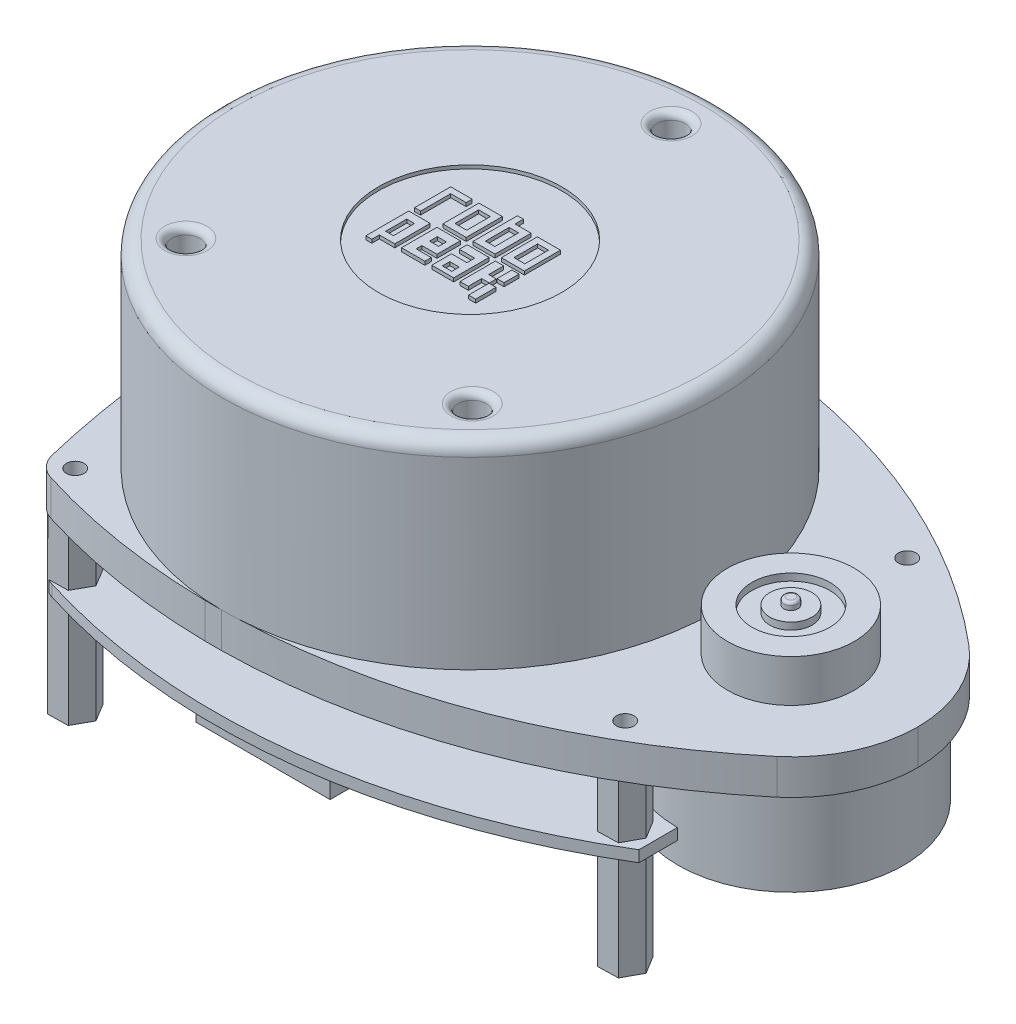
SolidWorks part; units mm, degrees
material "ABS"
ref_plane "Спереди" through (0, 0, 0) normal (0, 0, 1) x (1, 0, 0)
ref_plane "Сверху" through (0, 0, 0) normal (0, 1, 0) x (1, 0, 0)
ref_plane "Справа" through (0, 0, 0) normal (1, 0, 0) x (0, 0, -1)
sketch "Эскиз1" plane through (0, 0, 0) normal (0, 1, 0) x (1, 0, 0)
  line L1 (-49.25, 35) -> (49.25, 35)
  line L2 (-49.25, 35) -> (-49.25, -35)
  line L3 (-49.25, -35) -> (49.25, -35)
  line L4 (49.25, 35) -> (49.25, -35)
  line L5 (-49.25, 35) -> (49.25, -35) construction
  line L6 (-49.25, -35) -> (49.25, 35) construction
  point P0 (0, 0)
  dimension "D1" = 98.5
  dimension "D2" = 70
extrude "Бобышка-Вытянуть1" add sketch "Эскиз1" along normal blind 5
sketch "Эскиз2" plane through (0, 5, 0) normal (0, 1, 0) x (1, 0, 0)
  line L0 (-49.25, 35) -> (-49.25, -35) construction
  circle A0 centre (-14.25, 0) radius 35
  point P2 (-49.25, 0)
  point P3 (-49.25, 0)
extrude "Бобышка-Вытянуть2" add sketch "Эскиз2" along normal blind 28.1
sketch "Эскиз3" plane through (0, 33.1, 0) normal (0, 1, 0) x (1, 0, 0)
  line L0 (-14.25, 0) -> (-14.25, 50000) construction
  line L1 (-14.25, -20) -> (-26.2883, -20) construction
  line L2 (-49.25, -35) -> (-14.25, -35) construction
  circle A0 centre (-14.25, 28.5) radius 2
  circle A1 centre (-34.5539, -20) radius 2
  circle A2 centre (6.0539, -20) radius 2
  arc A3 (-49.25, 0) -> (-14.25, -35) centre (-14.25, 0) ccw construction
  circle A4 centre (-14.25, 0) radius 35 construction
  dimension "D2" = 4
  dimension "D1" = 6.5
  dimension "D3" = 15
  dimension "D4" = 28.5
  dimension "D5" = 28.5
extrude "Вырез-Вытянуть1" cut sketch "Эскиз3" against normal blind 5
fillet "Скругление1" radius 2 1 edges at (-14.25, 33.1, 35)
fillet "Скругление2" radius 1 3 edges at (6.0539, 33.1, 22) (-34.5539, 33.1, 22) (-14.25, 33.1, -26.5)
sketch "Эскиз4" plane through (0, 33.1, 0) normal (0, 1, 0) x (1, 0, 0)
  line L0 (-22.1152, -6.9149) -> (-22.1152, -0.8316)
  line L1 (-22.1152, -0.8316) -> (-19.0735, -0.8316)
  line L2 (-19.0735, -0.8316) -> (-19.0735, -5.8538)
  line L3 (-19.0735, -5.8538) -> (-21.2663, -5.8538)
  line L4 (-21.2663, -5.8538) -> (-21.2663, -6.9149)
  line L5 (-21.2663, -6.9149) -> (-22.1152, -6.9149)
  line L6 (-22.1152, 0) -> (-22.1152, 5.1201)
  line L7 (-22.1152, 5.1201) -> (-19.0735, 5.1201)
  line L8 (-19.0735, 5.1201) -> (-19.0735, 4.2707)
  line L9 (-19.0735, 4.2707) -> (-21.2663, 4.2707)
  line L10 (-21.2663, 4.2707) -> (-21.2663, 0)
  line L11 (-21.2663, 0) -> (-22.1152, 0)
  line L12 (-21.2663, -1.9579) -> (-20.1699, -1.9579)
  line L13 (-20.1699, -1.9579) -> (-20.1699, -4.9509)
  line L14 (-20.1699, -4.9509) -> (-21.2663, -4.9509)
  line L15 (-21.2663, -4.9509) -> (-21.2663, -1.9579)
  line L16 (-13.8296, 0) -> (-13.8296, 6.293)
  line L17 (-18.1168, 0) -> (-14.8003, 0)
  line L18 (-18.1168, 0) -> (-18.1168, 5.1201)
  line L19 (-18.1168, 5.1201) -> (-14.8003, 5.1201)
  line L20 (-14.8003, 0) -> (-14.8003, 5.1201)
  line L21 (-9.8255, 5.1201) -> (-6.5494, 5.1201)
  line L22 (-9.8255, 5.1201) -> (-9.8255, 0)
  line L23 (-9.8255, 0) -> (-6.5494, 0)
  line L24 (-6.5494, 5.1201) -> (-6.5494, 0)
  line L25 (-8.9357, 4.2707) -> (-7.3988, 4.2707)
  line L26 (-8.9357, 4.2707) -> (-8.9357, 0.9137)
  line L27 (-8.9357, 0.9137) -> (-7.3988, 0.9137)
  line L28 (-7.3988, 4.2707) -> (-7.3988, 0.9137)
  line L29 (-17.3079, 4.2707) -> (-15.6497, 4.2707)
  line L30 (-17.3079, 4.2707) -> (-17.3079, 0.9137)
  line L31 (-17.3079, 0.9137) -> (-15.6497, 0.9137)
  line L32 (-15.6497, 4.2707) -> (-15.6497, 0.9137)
  line L33 (-12.9802, 4.2707) -> (-11.6455, 4.2707)
  line L34 (-12.9802, 4.2707) -> (-12.9802, 0.9137)
  line L35 (-12.9802, 0.9137) -> (-11.6455, 0.9137)
  line L36 (-11.6455, 4.2707) -> (-11.6455, 0.9137)
  line L37 (-12.9802, -4.142) -> (-11.6455, -4.142)
  line L38 (-12.9802, -4.142) -> (-12.9802, -5.1936)
  line L39 (-12.9802, -5.1936) -> (-11.6455, -5.1936)
  line L40 (-11.6455, -4.142) -> (-11.6455, -5.1936)
  line L41 (-16.9439, -1.9579) -> (-15.6497, -1.9579)
  line L42 (-16.9439, -1.9579) -> (-16.9439, -3.0499)
  line L43 (-16.9439, -3.0499) -> (-15.6497, -3.0499)
  line L44 (-15.6497, -1.9579) -> (-15.6497, -3.0499)
  line L46 (-7.5508, -0.7643) -> (-6.5494, -0.7643)
  line L47 (-7.5508, -0.7643) -> (-7.5508, -2.8858)
  line L48 (-7.5508, -2.8858) -> (-6.5494, -2.8858)
  line L49 (-6.5494, -0.7643) -> (-6.5494, -2.8858)
  line L50 (-6.5494, -6.9149) -> (-7.5508, -6.9149)
  line L51 (-6.5494, -6.9149) -> (-6.5494, -4.0216)
  line L52 (-6.5494, -4.0216) -> (-7.5508, -4.0216)
  line L53 (-13.8296, 6.293) -> (-12.9802, 6.293)
  line L54 (-12.9802, 6.293) -> (-12.9802, 5.1201)
  line L55 (-12.9802, 5.1201) -> (-10.7153, 5.1201)
  line L56 (-10.7153, 5.1201) -> (-10.7153, 0)
  line L57 (-10.7153, 0) -> (-13.8296, 0)
  line L58 (-9.8255, -0.8316) -> (-8.6437, -0.8316)
  line L59 (-8.6437, -0.8316) -> (-8.6437, -2.9608)
  line L60 (-8.6437, -2.9608) -> (-7.5508, -2.9608)
  line L61 (-9.8255, -0.8316) -> (-9.8255, -5.8538)
  line L62 (-9.8255, -5.8538) -> (-8.6437, -5.8538)
  line L63 (-8.6437, -5.8538) -> (-8.6437, -3.9573)
  line L64 (-8.6437, -3.9573) -> (-7.5508, -3.9573)
  line L65 (-7.5508, -2.9608) -> (-7.5508, -3.9573)
  line L66 (-13.8296, -0.8316) -> (-10.7153, -0.8316)
  line L67 (-10.7153, -0.8316) -> (-10.7153, -5.8538)
  line L68 (-10.7153, -5.8538) -> (-13.8296, -5.8538)
  line L69 (-13.8296, -5.8538) -> (-13.8296, -3.0499)
  line L70 (-13.8296, -3.0499) -> (-11.6455, -3.0499)
  line L71 (-11.6455, -3.0499) -> (-11.6455, -1.9408)
  line L72 (-11.6455, -1.9408) -> (-13.8296, -1.9408)
  line L73 (-13.8296, -1.9408) -> (-13.8296, -0.8316)
  line L74 (-18.1168, -0.8316) -> (-14.8003, -0.8316)
  line L75 (-14.8003, -0.8316) -> (-14.8003, -4.142)
  line L76 (-14.8003, -4.142) -> (-16.9439, -4.142)
  line L77 (-16.9439, -4.142) -> (-16.9439, -4.9509)
  line L78 (-16.9439, -4.9509) -> (-14.8003, -4.9509)
  line L79 (-14.8003, -4.9509) -> (-14.8003, -5.8538)
  line L80 (-14.8003, -5.8538) -> (-18.1168, -5.8538)
  line L81 (-18.1168, -5.8538) -> (-18.1168, -0.8316)
  line L82 (-7.5508, -6.9149) -> (-7.5508, -4.0216)
  circle A0 centre (-14.25, 0) radius 13
  dimension "D1" = 26
extrude "Вырез-Вытянуть3" cut sketch "Эскиз4" against normal blind 0.5 contours A0 L50 L82 L52 L51 L72 L73 L66 L67 L68 L69 L70 L71 L56 L57 L16 L53 L54 L55 L10 L11 L6 L7 L8 L9 L4 L5 L0 L1 L2 L3 L20 L17 L18 L19 L21 L24 L23 L22 L46 L49 L48 L47 | L32 L29 L30 L31 | L36 L33 L34 L35 | L28 L25 L26 L27 | L44 L41 L42 L43 | L15 L14 L13 L12 | L37 L40 L39 L38 region at (-20.7181, 33.1, 3.4544) region at (-8.1672, 33.1, -2.5922) region at (-16.4788, 33.1, -2.5922) region at (-12.3129, 33.1, -2.5922) region at (-16.2968, 33.1, 2.5039) region at (-14.2871, 33.1, -0.0991)
sketch "Эскиз5" plane through (0, 5, 0) normal (0, 1, 0) x (1, 0, 0)
  line L0 (-42.25, 30.7255) -> (-42.25, -39.5827) construction
  line L1 (27.75, 26.9972) -> (27.75, -49973.0028) construction
  line L2 (-49.25, 0) -> (49950.75, 0) construction
  circle A0 centre (-14.25, 0) radius 33 construction
  circle A1 centre (-42.25, 28) radius 1.25
  circle A2 centre (27.75, 20) radius 1.25
  circle A3 centre (27.75, -20) radius 1.25
  circle A4 centre (-42.25, -28) radius 1.25
  point P4 (-14.25, 33)
  dimension "D1" = 28
  dimension "D3" = 2.5
  dimension "D2" = 42
  dimension "D4" = 28
  dimension "D5" = 20
extrude "Вырез-Вытянуть4" cut sketch "Эскиз5" against normal blind 5
sketch "Эскиз6" plane through (0, 5, 0) normal (0, 1, 0) x (1, 0, 0)
  line L0 (49.25, 0) -> (50049.25, 0) construction
  line L1 (49.25, -35) -> (49.25, 35) construction
  circle A0 centre (31.25, 0) radius 9
  arc A1 (-14.25, -35) -> (-14.25, 35) centre (-14.25, 0) ccw construction
  point P4 (49.25, 0)
  dimension "D1" = 18
  dimension "D2" = 45.5
extrude "Бобышка-Вытянуть3" add sketch "Эскиз6" along normal blind 7
sketch "Эскиз7" plane through (0, 12, 0) normal (0, 1, 0) x (1, 0, 0)
  circle A0 centre (31.25, 0) radius 9
  circle A1 centre (31.25, 0) radius 0.9935
extrude "Вырез-Вытянуть5" cut sketch "Эскиз7" against normal blind 1
sketch "Эскиз8" plane through (0, 11, 0) normal (0, 1, 0) x (1, 0, 0)
  circle A0 centre (31.25, 0) radius 3.0011
  circle A1 centre (31.25, 0) radius 5.5217
extrude "Вырез-Вытянуть6" cut sketch "Эскиз8" against normal blind 1
fillet "Скругление3" radius 0.4 1 edges at (31.25, 12, 0.9935)
sketch "Эскиз9" plane through (0, 5, 0) normal (0, 1, 0) x (1, 0, 0)
  circle A0 centre (31.25, 0) radius 16
  dimension "D1" = 32
extrude "Бобышка-Вытянуть4" add sketch "Эскиз9" against normal blind 18
sketch "Эскиз10" plane through (0, 0, 0) normal (0, -1, 0) x (1, 0, 0)
  line L0 (-49.25, 0) -> (49950.75, 0) construction
  line L1 (-40.8546, 25.4729) -> (-39.3638, 27.9449)
  line L2 (-39.3638, 27.9449) -> (-40.7592, 30.472)
  line L3 (-40.7592, 30.472) -> (-43.6454, 30.5271)
  line L4 (-43.6454, 30.5271) -> (-45.1362, 28.0551)
  line L5 (-45.1362, 28.0551) -> (-43.7408, 25.528)
  line L6 (-43.7408, 25.528) -> (-40.8546, 25.4729)
  line L7 (29.2571, 22.4621) -> (26.3713, 22.5363)
  line L8 (26.3713, 22.5363) -> (24.8642, 20.0742)
  line L9 (24.8642, 20.0742) -> (26.2429, 17.5379)
  line L10 (26.2429, 17.5379) -> (29.1287, 17.4637)
  line L11 (29.1287, 17.4637) -> (30.6358, 19.9258)
  line L12 (30.6358, 19.9258) -> (29.2571, 22.4621)
  line L13 (30.6358, -19.9258) -> (29.2571, -22.4621)
  line L14 (29.1287, -17.4637) -> (30.6358, -19.9258)
  line L15 (26.2429, -17.5379) -> (29.1287, -17.4637)
  line L16 (24.8642, -20.0742) -> (26.2429, -17.5379)
  line L17 (26.3713, -22.5363) -> (24.8642, -20.0742)
  line L18 (29.2571, -22.4621) -> (26.3713, -22.5363)
  line L19 (-43.7408, -25.528) -> (-40.8546, -25.4729)
  line L20 (-45.1362, -28.0551) -> (-43.7408, -25.528)
  line L21 (-43.6454, -30.5271) -> (-45.1362, -28.0551)
  line L22 (-40.7592, -30.472) -> (-43.6454, -30.5271)
  line L23 (-39.3638, -27.9449) -> (-40.7592, -30.472)
  line L24 (-40.8546, -25.4729) -> (-39.3638, -27.9449)
  circle A0 centre (-42.25, 28) radius 2.5 construction
  circle A1 centre (27.75, 20) radius 2.5 construction
  circle A2 centre (27.75, -20) radius 2.5 construction
  circle A3 centre (-42.25, -28) radius 2.5 construction
  point P17 (27.75, 20)
  dimension "D1" = 5
  dimension "D2" = 5
extrude "Бобышка-Вытянуть5" add sketch "Эскиз10" along normal blind 24.6
sketch "Эскиз11" plane through (0, 5, 0) normal (0, 1, 0) x (1, 0, 0)
  circle A0 centre (-14.25, 0) radius 26
  dimension "D1" = 52
extrude "Бобышка-Вытянуть6" add sketch "Эскиз11" against normal blind 8
fillet "Скругление4" radius 1 1 edges at (-14.25, -3, 26)
sketch "Эскиз12" plane through (0, 5, 0) normal (0, 1, 0) x (1, 0, 0)
  line L1 (49.25, -35) -> (49.25, 35) construction
  line L2 (-49.25, 0) -> (-50049.25, 0) construction
  line L4 (-54.0511, 37.7308) -> (52.2004, 37.7308)
  line L5 (-54.0511, 37.7308) -> (-54.0511, -37.8351)
  line L6 (-54.0511, -37.8351) -> (52.2004, -37.8351)
  line L7 (52.2004, 37.7308) -> (52.2004, -37.8351)
  arc A0 (-49.25, 0) -> (-45.5286, 27.9743) centre (86.6751, -3.8473) cw
  circle A1 centre (-14.25, 0) radius 35 construction
  arc A3 (49.25, 0) -> (42.909, 13.5993) centre (31.4018, -0.0442) ccw
  arc A4 (-49.25, 0) -> (-14.25, -35) centre (-14.25, 0) ccw construction
  arc A5 (-42.835, 30.8555) -> (42.909, 13.5993) centre (-15.6796, -55.8665) cw
  arc A6 (-45.5286, 27.9743) -> (-42.835, 30.8555) centre (-41.6397, 27.0383) cw
  arc A7 (-45.5286, -27.9743) -> (-42.835, -30.8555) centre (-41.6397, -27.0383) ccw
  arc A8 (-42.835, -30.8555) -> (42.909, -13.5993) centre (-15.6796, 55.8665) ccw
  arc A9 (49.25, 0) -> (42.909, -13.5993) centre (31.4018, 0.0442) cw
  arc A10 (-49.25, 0) -> (-45.5286, -27.9743) centre (86.6751, 3.8473) ccw
  dimension "D1" = 4
extrude "Вырез-Вытянуть7" cut sketch "Эскиз12" against normal blind 8
fillet "Скругление5" radius 100 1 edges at (-49.25, 2.5, 0)
sketch "Эскиз13" plane through (0, 0, 0) normal (0, -1, 0) x (1, 0, 0)
  line L0 (31.5536, 21.8603) -> (31.5536, 16.4)
  line L1 (31.5536, -16.4) -> (31.5536, -21.8603)
  arc A0 (-49.0982, 0) -> (-45.3768, 27.9743) centre (86.8269, -3.8473) cw
  arc A1 (31.5536, 16.4) -> (31.5536, -16.4) centre (31.5536, 0) ccw
  arc A2 (-42.6831, 30.8555) -> (31.5536, 21.8603) centre (-15.5278, -55.8665) cw
  arc A3 (-45.3768, 27.9743) -> (-42.6831, 30.8555) centre (-41.4878, 27.0383) cw
  arc A4 (-45.3768, -27.9743) -> (-42.6831, -30.8555) centre (-41.4878, -27.0383) ccw
  arc A5 (-42.6831, -30.8555) -> (31.5536, -21.8603) centre (-15.5278, 55.8665) ccw
  arc A7 (-49.0982, 0) -> (-45.3768, -27.9743) centre (86.8269, 3.8473) ccw
  arc A8 (-48.5248, 10.6929) -> (-48.5248, -10.6929) centre (50.9018, 0) ccw construction
  point P16 (-49.0982, 0)
  point P21 (-49.0982, 0)
  dimension "D1" = 4
  dimension "D2" = 32.8
extrude "Бобышка-Вытянуть7" add sketch "Эскиз13" along normal blind 1.6 from offset 8
sketch "Эскиз14" plane through (0, -9.6, 0) normal (0, -1, 0) x (1, 0, 0)
  line L1 (-24.0982, 30) -> (-4.0982, 30)
  line L2 (-24.0982, 30) -> (-24.0982, 25)
  line L3 (-24.0982, 25) -> (-4.0982, 25)
  line L4 (-4.0982, 30) -> (-4.0982, 25)
  circle A0 centre (-14.25, 0) radius 35 construction
  point P4 (-14.0982, 30)
  dimension "D1" = 5
  dimension "D2" = 20
  dimension "D3" = 35
  dimension "D4" = 30
extrude "Бобышка-Вытянуть8" add sketch "Эскиз14" along normal blind 6
chamfer "Фаска1" distance 1 angle 45 1 edges at (-24.0982, -12.6, 30)
